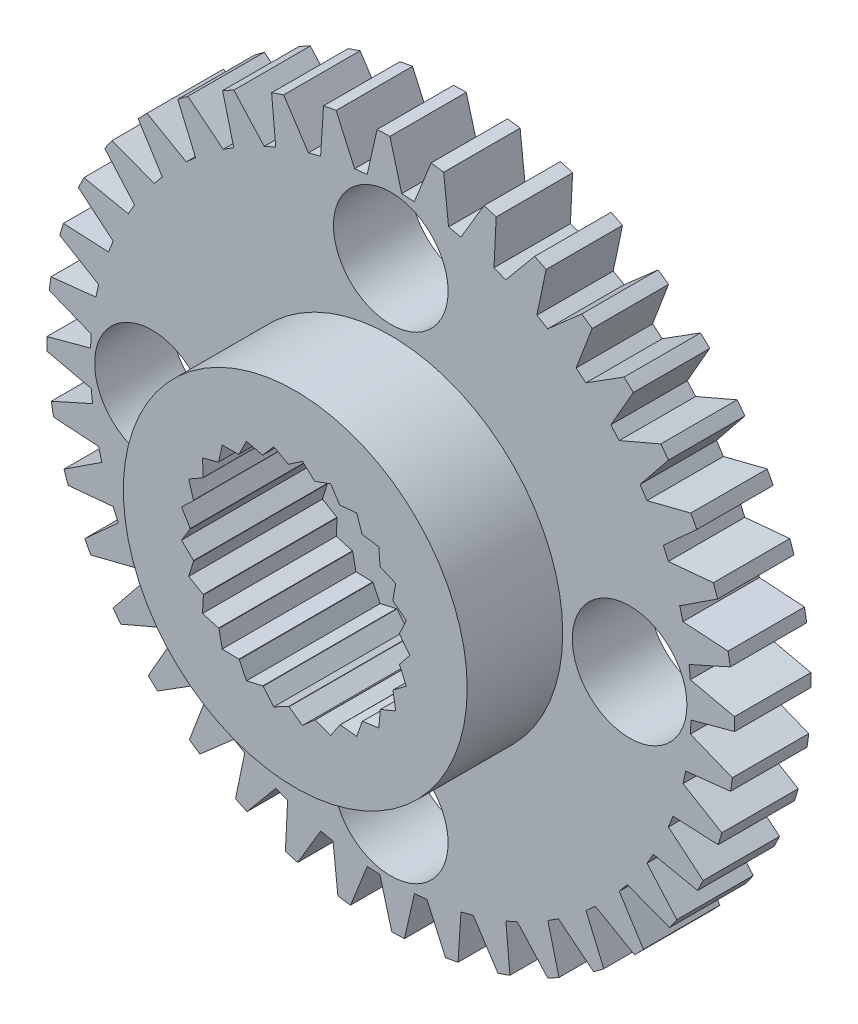
SolidWorks part; units mm, degrees
other "Markup1"
sketch "Sketch8" plane through (-15, 14.9981, 4.5) normal (-0.0348, 0.0108, 0.9993) x (0.9952, -0.0909, 0.0356)
ref_plane "Front Plane" through (0, 0, 0) normal (0, 0, 1) x (1, 0, 0)
ref_plane "Top Plane" through (0, 0, 0) normal (0, 1, 0) x (1, 0, 0)
ref_plane "Right Plane" through (0, 0, 0) normal (1, 0, 0) x (0, 0, -1)
sketch "Sketch1" plane through (0, 0, 0) normal (0, 0, 1) x (1, 0, 0)
  circle A0 centre (0, 0) radius 9
  circle A1 centre (0, 0) radius 6.25 construction
  circle A2 centre (0, 6.25) radius 1.5
  circle A3 centre (6.25, 0) radius 1.5
  circle A4 centre (0, -6.25) radius 1.5
  circle A5 centre (-6.25, 0) radius 1.5
  circle A6 centre (0, 0) radius 4.5
  circle A7 centre (0, 0) radius 2.75 construction
  dimension "D1" = 18
  dimension "D2" = 3
  dimension "5" = 5.5
  dimension "D5" = 3.5
  dimension "D3" = 4
extrude "Boss-Extrude1" add sketch "Sketch1" along normal blind 2
extrude "Boss-Extrude2" add sketch "Sketch1<2>" along normal blind 4.5 contours A6 region at (0, 0, 0)
sketch "Sketch1<2>" plane through (0, 0, 0) normal (0, 0, 1) x (1, 0, 0) same geometry as "Sketch1"
sketch "Sketch2" plane through (0, 0, 0) normal (0, 0, -1) x (-1, 0, 0)
  circle A0 centre (0, 0) radius 1.5
extrude "Cut-Extrude1" cut sketch "Sketch2" against normal blind 4.5
sketch "Sketch3" plane through (0, 0, 4.5) normal (0, 0, 1) x (1, 0, 0)
  circle A0 centre (0, 0) radius 2.75
extrude "Cut-Extrude2" cut sketch "Sketch3" against normal blind 3.5
sketch "Sketch4" plane through (0, 0, 4.5) normal (0, 0, 1) x (1, 0, 0)
  line L0 (0, 0) -> (-3, 0)
  line L1 (0, 0) -> (-2.9763, 0.376)
  line L2 (0, 0) -> (-2.9083, 0.7359)
  line L3 (-2.75, 0) -> (-2.9763, 0.376)
  line L4 (-2.666, 0.6746) -> (-2.9763, 0.376)
  circle A0 centre (0, 0) radius 3
  circle A1 centre (0, 0) radius 2.75 construction
  circle A2 centre (0, 0) radius 2.75 construction
  circle A3 centre (0, 0) radius 2.75
  circle M6 centre (0, 0) radius 2.75
  dimension "D1" = 7.2
  dimension "D2" = 14.2
extrude "Cut-Extrude3" cut sketch "Sketch4" against normal blind 3.5 contours L4 L1 M6 | L3 L1 M6 region at (-2.8205, 0.2422, 4.5) region at (-2.7928, 0.4638, 4.5)
pattern_circular "CirPattern1" count 25 over 360 about axis through (0, 0, 4.5) along (0, 0, -1) of "Cut-Extrude3" reverse direction yes
sketch "Sketch5" plane through (0, 0, 0) normal (0, 0, -1) x (-1, 0, 0)
  circle A0 centre (0, 0) radius 3.5
  circle A1 centre (0, 0) radius 1.5
  circle A2 centre (0, 0) radius 1.5 construction
  dimension "11" = 7
extrude "Boss-Extrude3" add sketch "Sketch5" along normal blind 3
sketch "Sketch7" plane through (0, 0, 2) normal (0, 0, 1) x (1, 0, 0)
  line L1 (-7.615, 4.9053) -> (-7.3111, 5.2768) construction
  line L8 (-7.615, 4.9053) -> (-6.9746, 3.8905) construction
  line L9 (-6.9746, 3.8905) -> (-6.1895, 4.8502) construction
  line L10 (-6.1895, 4.8502) -> (-7.3111, 5.2768)
  line L11 (-6.1895, 4.8502) -> (-5.9805, 5.1057)
  line L12 (-5.9805, 5.1057) -> (-6.6209, 6.1205)
  line L13 (-6.6209, 6.1205) -> (-7.3111, 5.2768)
  line L14 (-7.3111, 5.2768) -> (-7.615, 4.9053) construction
  circle A0 centre (0, 0) radius 9
  circle A1 centre (0, 0) radius 9 construction
  circle M14 centre (0, 0) radius 9
  dimension "D1" = 0.48
  dimension "D7" = 1.09
  dimension "D2" = 1.2
  dimension "D3" = 1.2
  dimension "D4" = 0.33
  dimension "D5" = 1.24
  dimension "D6" = 1.2
extrude "Cut-Extrude11" cut sketch "Sketch7" against normal blind 3.6 contours L11 L12 L10 M14 region at (-6.6014, 5.4004, 2)
pattern_circular "CirPattern4" count 40 over 360 about axis through (0, 0, 2) along (0, 0, -1) of "Cut-Extrude11"
